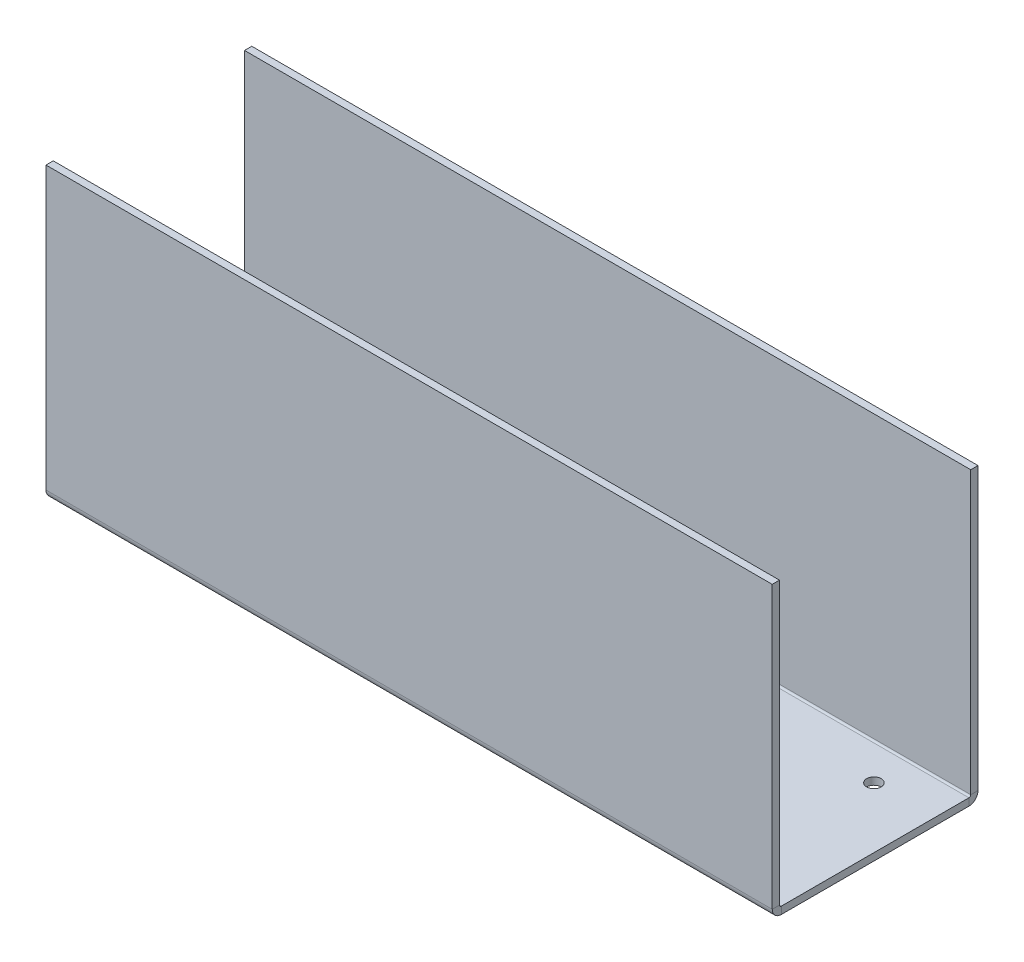
SolidWorks part; units mm, degrees
note: The reader was unsure of these and kept them because the rebuilt part matched: flange length of "Edge-Flange1".
ref_plane "Front Plane" through (0, 0, 0) normal (0, 0, 1) x (1, 0, 0)
ref_plane "Top Plane" through (0, 0, 0) normal (0, 1, 0) x (1, 0, 0)
ref_plane "Right Plane" through (0, 0, 0) normal (1, 0, 0) x (0, 0, -1)
sketch "Sketch1" plane through (0, 0, 0) normal (0, 1, 0) x (1, 0, 0)
  line L1 (-150, 42.5) -> (150, 42.5)
  line L2 (-150, 42.5) -> (-150, -42.5)
  line L3 (-150, -42.5) -> (150, -42.5)
  line L4 (150, 42.5) -> (150, -42.5)
  line L5 (-150, 42.5) -> (150, -42.5) construction
  line L6 (-150, -42.5) -> (150, 42.5) construction
  point P0 (0, 0)
  dimension "D1" = 300
  dimension "D2" = 85
base flange "Base-Flange2" sketch "Sketch1" thickness 3 reverse thickness direction no parameters "D1"=0.7366
edge flange "Edge-Flange1" sketch "Sketch14" flange profiles "Sketch14", "Sketch15" flange angle 90 flange length 120 flange position material inside bend radius 0.7366 thickness 3 relief rectangular parameters "D6"=10, "D8"=1
sketch "Sketch14" plane through (0, 0, 42.5) normal (0, 0, 1) x (1, 0, 0)
  line L0 (-150, 0) -> (150, 0) construction
  line L1 (-150, 0) -> (150, 0)
  line L2 (-150, 0) -> (-150, 117)
  line L3 (-150, 117) -> (150, 117)
  line L4 (150, 117) -> (150, 0)
sketch "Sketch15" plane through (0, 0, -42.5) normal (0, 0, -1) x (-1, 0, 0)
  line L0 (-150, 0) -> (150, 0) construction
  line L1 (-150, 0) -> (150, 0)
  line L2 (-150, 0) -> (-150, 117)
  line L3 (-150, 117) -> (150, 117)
  line L4 (150, 117) -> (150, 0)
bend "EdgeBend1" bend radius 0.7366 bend angle 90 parameters "D5"=1
bend "EdgeBend2" bend radius 0.7366 bend angle 90 parameters "D5"=2
sketch "Sketch17" plane through (0, 0, 0) normal (0, 1, 0) x (1, 0, 0)
  line L0 (-150, 38.7634) -> (-150, -38.7634) construction
  line L1 (-150, 42.5) -> (150, 42.5) construction
  circle A0 centre (-125, 24.5) radius 3
  circle A1 centre (-125, -20.5) radius 3
  circle A2 centre (125, 24.5) radius 3
  circle A3 centre (125, -20.5) radius 3
  dimension "D2" = 6
  dimension "D5" = 250
  dimension "D1" = 25
  dimension "D3" = 45
  dimension "D4" = 18
extrude "Cut-Extrude1" cut sketch "Sketch17" against normal blind 10 normal cut yes
sketch "Bend-Lines3" [suppressed] plane through (0, 0, 0) normal (0, 1, 0) x (1, 0, 0)
sketch "Bounding-Box3" [suppressed] plane through (0, 0, 0) normal (0, 1, 0) x (1, 0, 0)
sheet metal parameters "Sheet-Metal2" thickness 3 parameters "D1"=0.7366
flat pattern "Flat-Pattern2" [suppressed]
sketch "Bend-Lines4" plane through (0, 0, 0) normal (0, 1, 0) x (1, 0, 0)
sketch3d "Bounding-Box4" [suppressed]
  line L0 (-175, -40, 0) -> (175, -40, 0) construction
  line L1 (-175, 40, 0) -> (175, 40, 0) construction
  line L2 (-175, -40, 0) -> (-175, 40, 0) construction
  line L3 (175, -40, 0) -> (175, 40, 0) construction
sheet metal parameters "Sheet-Metal3" thickness 3 parameters "D1"=0.7366
flat pattern "Flat-Pattern2"
sketch "Bend-Lines4" plane through (0, 0, 0) normal (0, 1, 0) x (1, 0, 0)
  line L0 (250, 38.02) -> (-250, 38.02) construction
  line L1 (-250, -38.02) -> (250, -38.02) construction
  line L2 (250, 38.02) -> (-250, 38.02) construction
  line L3 (-250, -38.02) -> (250, -38.02) construction
sketch3d "Bounding-Box4" [suppressed]
  line L0 (250, -156.04, 0) -> (-250, -156.04, 0) construction
  line L1 (250, 156.04, 0) -> (-250, 156.04, 0) construction
  line L2 (250, -156.04, 0) -> (250, 156.04, 0) construction
  line L3 (-250, -156.04, 0) -> (-250, 156.04, 0) construction
bend of the flat pattern "Flatten-<EdgeBend1>1"
bend of the flat pattern "Flatten-<EdgeBend2>1"
sheet metal parameters "Sheet-Metal4" thickness 3 parameters "D1"=0.7366
flat pattern "Flat-Pattern2"
sketch "Bend-Lines4" plane through (0, 0, 0) normal (0, 1, 0) x (1, 0, 0)
  line L0 (150, 40.52) -> (-150, 40.52) construction
  line L1 (-150, -40.52) -> (150, -40.52) construction
  line L2 (150, 40.52) -> (-150, 40.52) construction
  line L3 (-150, -40.52) -> (150, -40.52) construction
sketch3d "Bounding-Box4" [suppressed]
  line L0 (-150, 158.54, 0) -> (-150, -158.54, 0) construction
  line L1 (150, 158.54, 0) -> (150, -158.54, 0) construction
  line L2 (-150, 158.54, 0) -> (150, 158.54, 0) construction
  line L3 (-150, -158.54, 0) -> (150, -158.54, 0) construction
bend of the flat pattern "Flatten-<EdgeBend1>1"
bend of the flat pattern "Flatten-<EdgeBend2>1"
